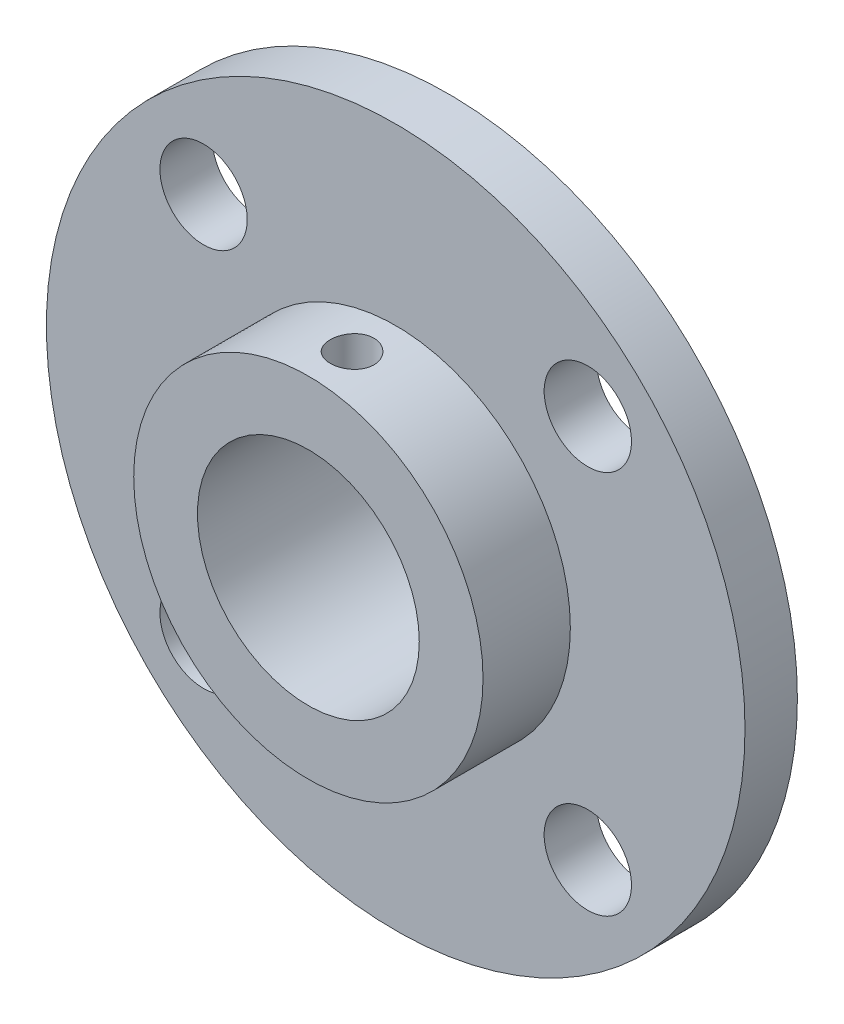
SolidWorks part; units mm, degrees
ref_plane "Front Plane" through (0, 0, 0) normal (0, 0, 1) x (1, 0, 0)
ref_plane "Top Plane" through (0, 0, 0) normal (0, 1, 0) x (1, 0, 0)
ref_plane "Right Plane" through (0, 0, 0) normal (1, 0, 0) x (0, 0, -1)
sketch "Sketch1" plane through (0, 0, 0) normal (0, 0, 1) x (1, 0, 0)
  circle A0 centre (0, 0) radius 20
  dimension "D1" = 40
extrude "Boss-Extrude1" add sketch "Sketch1" along normal blind 3
sketch "Sketch2" plane through (0, 0, 3) normal (0, 0, 1) x (1, 0, 0)
  circle A0 centre (0, 0) radius 10
  dimension "D1" = 20
extrude "Boss-Extrude2" add sketch "Sketch2" along normal blind 5
sketch "Sketch18" plane through (0, 0, 0) normal (0, 0, -1) x (-1, 0, 0)
  circle A0 centre (0, 0) radius 9
  dimension "D1" = 18
extrude "Boss-Extrude3" add sketch "Sketch18" along normal blind 2
sketch "Sketch4" plane through (0, 0, 8) normal (0, 0, 1) x (1, 0, 0)
  circle A0 centre (0, 0) radius 6.35
  dimension "D1" = 12.7
extrude "Cut-Extrude1" cut sketch "Sketch4" against normal through all
ref_plane "Plane2" through (0, 0, 5.5) normal (0, 0, 1) x (1, 0, 0)
hole_wizard "M3 Tapped Hole1" positions "3DSketch7" profile "Sketch15" tap size "M3" standard "ISO" end condition up to next
sketch3d "3DSketch7"
  point P0 (0, 10, 5.5)
sketch "Sketch15" plane through (0, 10, 5.5) normal (1, 0, 0) x (0, 0, 1)
  line L0 (0, 0) -> (0, 3.65)
  line L1 (0, 3.65) -> (1.25, 3.65)
  line L2 (1.25, 3.65) -> (1.25, 0)
  line L5 (1.25, 0) -> (0, 0)
  line L11 (0, -6.35) -> (0, 107.95) construction
  dimension "Thru Tap Drill Dia." = 2.5
  dimension "Thru Tap Drill Depth" = 3.65
cosmetic thread "Hole Thread1" parameters "D2"=3
sketch "Sketch16" plane through (0, 0, 3) normal (0, 0, 1) x (1, 0, 0)
  line L0 (0, 0) -> (34.2865, 0) construction
  line L1 (0, 0) -> (11, 11) construction
  point P0 (11, 11)
  dimension "D1" = 11
  dimension "D2" = 45
hole_wizard "Ø5.0 (5) Diameter Hole1" positions "3DSketch8" profile "Sketch17" hole size "Ø5.0" standard "ISO" end condition through all
sketch3d "3DSketch8"
  point P0 (11, 11, 3)
sketch "Sketch17" plane through (11, 11, 3) normal (1, 0, 0) x (0, -1, 0)
  line L0 (0, 0) -> (0, 5)
  line L1 (0, 5) -> (2.5, 5)
  line L2 (2.5, 5) -> (2.5, 0)
  line L5 (2.5, 0) -> (0, 0)
  line L11 (0, -6.35) -> (0, 107.95) construction
  dimension "Thru Hole Dia." = 5
  dimension "Thru Hole Depth" = 5
pattern_circular "CirPattern1" count 4 over 360 about axis through (0, 0, 8) along (0, 0, -1) of "Ø5.0 (5) Diameter Hole1"
